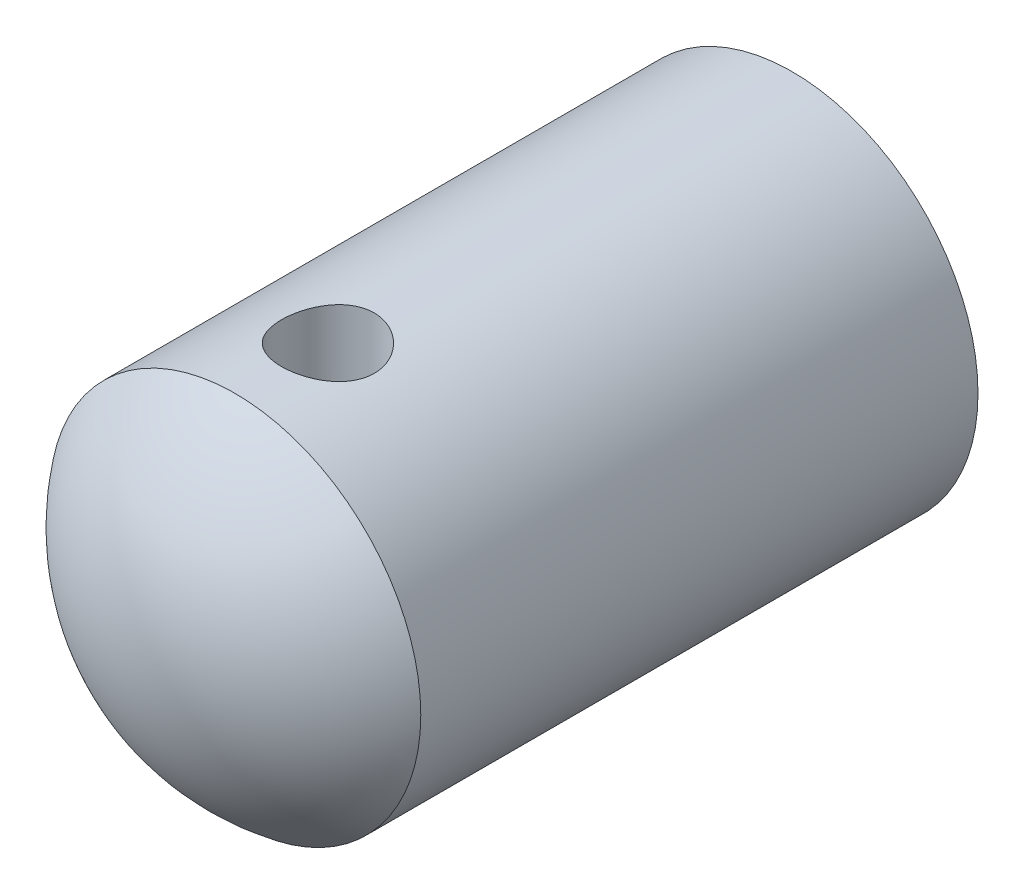
SolidWorks part; units mm, degrees
ref_plane "Ön Düzlem" through (0, 0, 0) normal (0, 0, 1) x (1, 0, 0)
ref_plane "Üst Düzlem" through (0, 0, 0) normal (0, 1, 0) x (1, 0, 0)
ref_plane "Sağ Düzlem" through (0, 0, 0) normal (1, 0, 0) x (0, 0, -1)
sketch "Çizim1" plane through (0, 0, 0) normal (0, 0, 1) x (1, 0, 0)
  circle A0 centre (0, 0) radius 40
  dimension "D1" = 80
extrude "Yükseklik-Ekstrüzyon1" add sketch "Çizim1" along normal blind 120
ref_plane "Düzlem1" through (0, 20, 0) normal (0, 1, 0) x (1, 0, 0)
sketch "Çizim2" plane through (0, 20, 0) normal (0, 1, 0) x (1, 0, 0)
  circle A0 centre (0, -100) radius 10
  dimension "D1" = 20
  dimension "D2" = 100
extrude "Kes-Ekstrüzyon1" cut sketch "Çizim2" along normal blind 30
mirror "Aynalama1" about plane through (0, 0, 0) normal (0, 1, 0) of "Kes-Ekstrüzyon1"
dome "Kubbe1" faces to dome 1 distance 20 reverse direction no elliptical dome no face at (40, 0, 120) parameters "D1"=20
